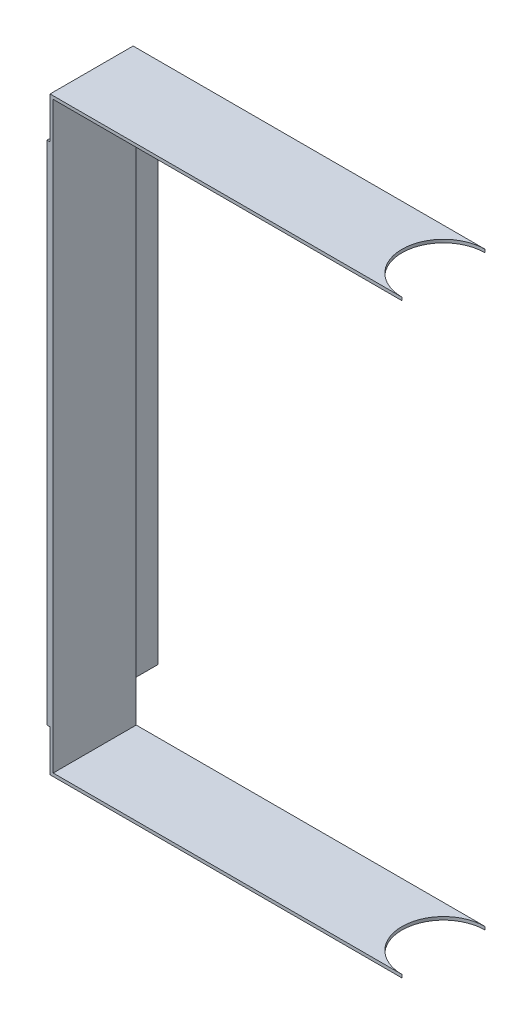
SolidWorks part; units mm, degrees
ref_plane "前视基准面" through (0, 0, 0) normal (0, 0, 1) x (1, 0, 0)
ref_plane "上视基准面" through (0, 0, 0) normal (0, 1, 0) x (1, 0, 0)
ref_plane "右视基准面" through (0, 0, 0) normal (1, 0, 0) x (0, 0, -1)
sketch "草图1" plane through (0, 0, 0) normal (0, 0, 1) x (1, 0, 0)
  line L0 (0, 15.7413) -> (-169.5, 15.7413)
  line L1 (-169.5, 15.7413) -> (-169.5, -268.2587)
  line L2 (-169.5, -268.2587) -> (0, -268.2587)
  line L3 (0, -268.2587) -> (0, -266.7587)
  line L4 (0, -266.7587) -> (-168, -266.7587)
  line L5 (0, 15.7413) -> (0, 14.2413)
  line L6 (0, 14.2413) -> (-168, 14.2413)
  line L7 (-168, 14.2413) -> (-168, -266.7587)
extrude "凸台-拉伸1" add sketch "草图1" along normal blind 40
sketch "草图2" plane through (0, -268.2587, 0) normal (0, -1, 0) x (-1, 0, 0)
  line L0 (0, -40) -> (0, 0) construction
  circle A0 centre (0, -20) radius 20
extrude "切除-拉伸1" cut sketch "草图2" against normal blind 336
sketch "草图3" plane through (-169.5, 0, 0) normal (-1, 0, 0) x (0, 0, 1)
  line L0 (40, 15.7413) -> (40, -4.2587) construction
  line L1 (40, 15.7413) -> (40, -268.2587) construction
  line L2 (40, -4.2587) -> (-12, -4.2587)
  line L3 (-12, -4.2587) -> (-12, -248.2587)
  line L4 (-12, -248.2587) -> (40, -248.2587)
  line L5 (40, -248.2587) -> (40, -4.2587)
extrude "凸台-拉伸2" add sketch "草图3" along normal blind 1.5
